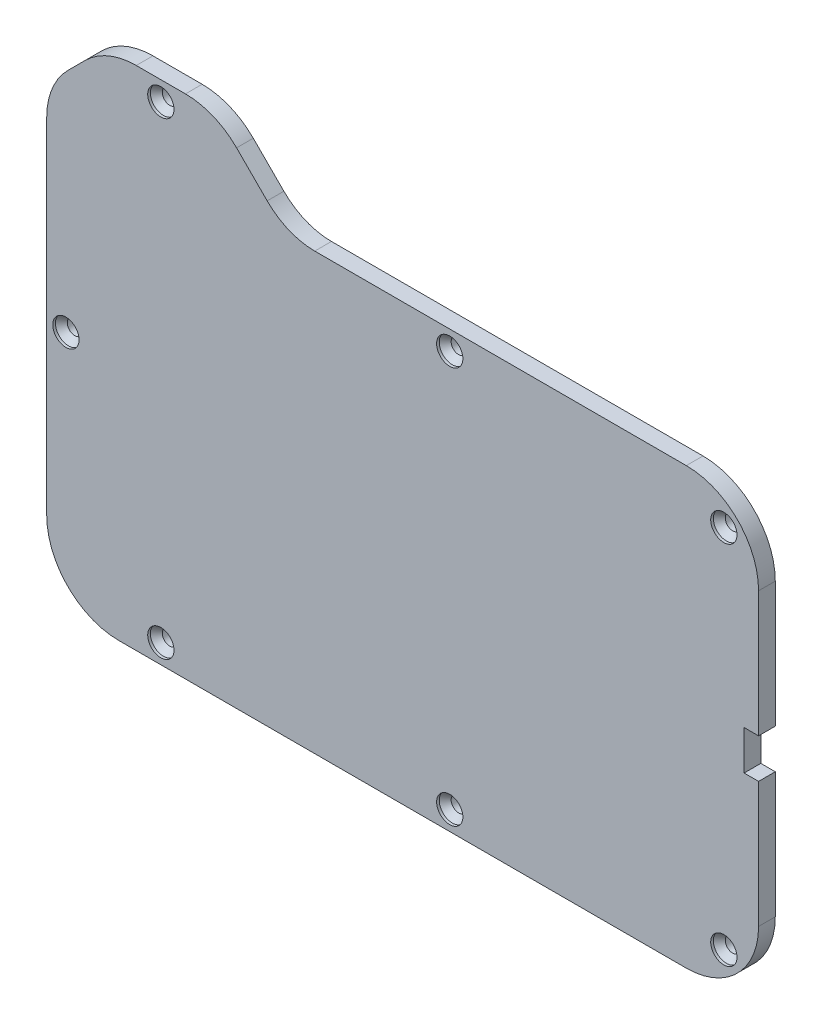
SolidWorks part; units mm, degrees
ref_plane "Front Plane" through (0, 0, 0) normal (0, 0, 1) x (1, 0, 0)
ref_plane "Top Plane" through (0, 0, 0) normal (0, 1, 0) x (1, 0, 0)
ref_plane "Right Plane" through (0, 0, 0) normal (1, 0, 0) x (0, 0, -1)
sketch "Sketch1" plane through (0, 0, 0) normal (0, 0, 1) x (1, 0, 0)
  line L51 (143.9081, 20.4605) -> (143.9081, 75.7605) construction
  line L52 (130.0581, 89.6105) -> (59.3752, 89.6105) construction
  line L53 (50.3949, 93.3302) -> (44.5712, 99.1539) construction
  line L54 (34.7778, 103.2105) -> (25.4148, 103.2105) construction
  line L55 (15.6214, 99.1539) -> (12.3411, 95.8737) construction
  line L56 (8.2846, 86.0802) -> (8.2846, 20.4605) construction
  line L57 (22.1346, 6.6105) -> (130.0581, 6.6105) construction
  line L58 (143.8081, 20.4605) -> (143.8081, 44.3605)
  line L59 (130.0581, 89.5105) -> (59.3752, 89.5105)
  line L60 (50.3242, 93.2595) -> (44.5005, 99.0832)
  line L61 (34.7778, 103.1105) -> (25.4148, 103.1105)
  line L62 (15.6921, 99.0832) -> (12.4118, 95.803)
  line L63 (8.3846, 86.0802) -> (8.3846, 20.4605)
  line L64 (22.1346, 6.7105) -> (130.0581, 6.7105)
  line L65 (143.8081, 48.1105) -> (141.0581, 48.1105) construction
  line L66 (141.0581, 44.3605) -> (141.0581, 51.8605)
  line L67 (141.0581, 51.8605) -> (143.8081, 51.8605)
  line L68 (141.0581, 44.3605) -> (143.8081, 44.3605)
  line L69 (143.8081, 51.8605) -> (143.8081, 75.7605)
  line L70 (143.8081, 51.8605) -> (143.8081, 44.3605) construction
  arc A71 (130.0581, 6.6105) -> (143.9081, 20.4605) centre (130.0581, 20.4605) ccw construction
  arc A72 (143.9081, 75.7605) -> (130.0581, 89.6105) centre (130.0581, 75.7605) ccw construction
  arc A73 (50.3949, 93.3302) -> (59.3752, 89.6105) centre (59.3752, 102.3105) ccw construction
  arc A74 (44.5712, 99.1539) -> (34.7778, 103.2105) centre (34.7778, 89.3605) ccw construction
  arc A75 (25.4148, 103.2105) -> (15.6214, 99.1539) centre (25.4148, 89.3605) ccw construction
  arc A76 (12.3411, 95.8737) -> (8.2846, 86.0802) centre (22.1346, 86.0802) ccw construction
  arc A77 (8.2846, 20.4605) -> (22.1346, 6.6105) centre (22.1346, 20.4605) ccw construction
  circle A78 centre (12.0346, 52.4704) radius 1.425
  circle A79 centre (30.0963, 99.4605) radius 1.425
  circle A80 centre (85.0537, 85.8605) radius 1.425
  circle A81 centre (137.1998, 82.9023) radius 1.425
  circle A82 centre (137.1998, 13.3187) radius 1.425
  circle A83 centre (85.0537, 10.3605) radius 1.425
  circle A84 centre (30.0963, 10.3605) radius 1.425
  arc A85 (143.8081, 75.7605) -> (130.0581, 89.5105) centre (130.0581, 75.7605) ccw
  arc A86 (50.3242, 93.2595) -> (59.3752, 89.5105) centre (59.3752, 102.3105) ccw
  arc A87 (44.5005, 99.0832) -> (34.7778, 103.1105) centre (34.7778, 89.3605) ccw
  arc A88 (25.4148, 103.1105) -> (15.6921, 99.0832) centre (25.4148, 89.3605) ccw
  arc A89 (12.4118, 95.803) -> (8.3846, 86.0802) centre (22.1346, 86.0802) ccw
  arc A90 (8.3846, 20.4605) -> (22.1346, 6.7105) centre (22.1346, 20.4605) ccw
  arc A91 (130.0581, 6.7105) -> (143.8081, 20.4605) centre (130.0581, 20.4605) ccw
  point P125 (141.0581, 48.1105)
extrude "Boss-Extrude1" add sketch "Sketch1" along normal blind 3.175
sketch "Sketch2" plane through (0, 0, 3.175) normal (0, 0, 1) x (1, 0, 0)
  circle A0 centre (137.1998, 82.9023) radius 2.5
  circle A1 centre (137.1998, 13.3187) radius 2.5
  circle A2 centre (85.0537, 10.3605) radius 2.5
  circle A3 centre (30.0963, 10.3605) radius 2.5
  circle A4 centre (12.0346, 52.4704) radius 2.5
  circle A5 centre (30.0963, 99.4605) radius 2.5
  circle A6 centre (85.0537, 85.8605) radius 2.5
extrude "Cut-Extrude1" cut sketch "Sketch2" against normal blind 0.5
sketch "Sketch3" plane through (0, 0, 2.675) normal (0, 0, 1) x (1, 0, 0)
  circle A0 centre (30.0963, 10.3605) radius 2.5 construction
  circle A1 centre (85.0537, 10.3605) radius 2.5
  circle A2 centre (85.0537, 10.3605) radius 2.5
  circle A3 centre (12.0346, 52.4704) radius 2.5 construction
  circle A4 centre (30.0963, 99.4605) radius 2.5 construction
  circle A5 centre (85.0537, 85.8605) radius 2.5 construction
  circle A6 centre (137.1998, 82.9023) radius 2.5 construction
  circle A7 centre (137.1998, 13.3187) radius 2.5 construction
  circle A8 centre (30.0963, 10.3605) radius 2.5
  circle A9 centre (12.0346, 52.4704) radius 2.5
  circle A10 centre (30.0963, 99.4605) radius 2.5
  circle A11 centre (85.0537, 85.8605) radius 2.5
  circle A12 centre (137.1998, 82.9023) radius 2.5
  circle A13 centre (137.1998, 13.3187) radius 2.5
  dimension "D1" = 0
extrude "Cut-Extrude2" cut sketch "Sketch3" against normal blind 1.2 draft 42
